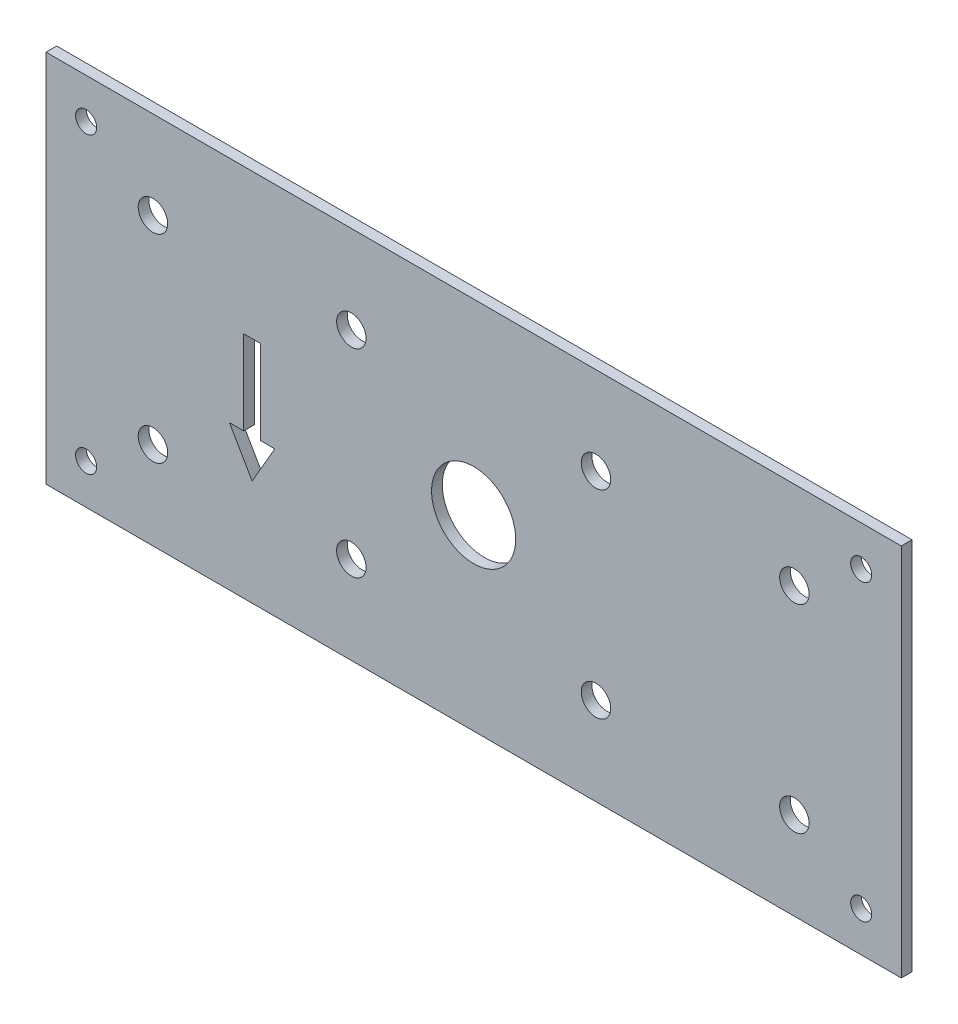
SolidWorks part; units mm, degrees
ref_plane "Front Plane" through (0, 0, 0) normal (0, 0, 1) x (1, 0, 0)
ref_plane "Top Plane" through (0, 0, 0) normal (0, 1, 0) x (1, 0, 0)
ref_plane "Right Plane" through (0, 0, 0) normal (1, 0, 0) x (0, 0, -1)
sketch "Sketch2" plane through (0, 0, 0) normal (0, 0, 1) x (1, 0, 0)
  line L0 (-29.06, 23.57) -> (-76.2, 23.57) construction
  line L1 (-101.6, -44.45) -> (101.6, -44.45)
  line L2 (-101.6, -44.45) -> (-101.6, 44.45)
  line L3 (-101.6, 44.45) -> (101.6, 44.45)
  line L4 (101.6, -44.45) -> (101.6, 44.45)
  line L5 (-101.6, -44.45) -> (101.6, 44.45) construction
  line L6 (-101.6, 44.45) -> (101.6, -44.45) construction
  line L7 (-76.2, 23.57) -> (-76.2, -23.57) construction
  line L8 (-76.2, -23.57) -> (-29.06, -23.57) construction
  line L9 (-29.06, -23.57) -> (-29.06, 23.57) construction
  line L10 (-76.2, 0) -> (-101.6, 0) construction
  line L12 (29.06, -23.57) -> (76.2, -23.57) construction
  line L13 (76.2, -23.57) -> (76.2, 23.57) construction
  line L14 (76.2, 23.57) -> (29.06, 23.57) construction
  line L15 (29.06, 23.57) -> (29.06, -23.57) construction
  line L17 (76.2, 0) -> (101.6, 0) construction
  circle A11 centre (-76.2, 23.57) radius 3.5
  circle A12 centre (-29.06, 23.57) radius 3.5
  circle A13 centre (-29.06, -23.57) radius 3.5
  circle A14 centre (-76.2, -23.57) radius 3.5
  circle A15 centre (29.06, -23.57) radius 3.5
  circle A16 centre (76.2, -23.57) radius 3.5
  circle A17 centre (76.2, 23.57) radius 3.5
  circle A18 centre (29.06, 23.57) radius 3.5
  circle A19 centre (0, 0) radius 10
  point P0 (0, 0)
  point P17 (101.6, 0)
  point P23 (-101.6, 0)
  dimension "D3" = 7
  dimension "D6" = 20
  dimension "D1" = 47.14
  dimension "D2" = 88.9
  dimension "D4" = 203.2
  dimension "D5" = 25.4
extrude "Boss-Extrude1" add sketch "Sketch2" along normal mid plane 2.54
sketch "Sketch3" plane through (0, 0, 1.27) normal (0, 0, 1) x (1, 0, 0)
  line L0 (-101.6, 34.925) -> (-92.075, 34.925) construction
  line L1 (-101.6, 44.45) -> (-101.6, -44.45) construction
  line L2 (-92.075, 34.925) -> (-92.075, 44.45) construction
  line L3 (101.6, 44.45) -> (-101.6, 44.45) construction
  line L4 (92.075, 44.45) -> (92.075, 34.925) construction
  line L5 (92.075, 34.925) -> (101.6, 34.925) construction
  line L6 (101.6, -44.45) -> (101.6, 44.45) construction
  line L7 (92.075, -44.45) -> (92.075, -34.925) construction
  line L8 (-101.6, -44.45) -> (101.6, -44.45) construction
  line L9 (92.075, -34.925) -> (101.6, -34.925) construction
  line L10 (-92.075, -44.45) -> (-92.075, -34.925) construction
  line L11 (-92.075, -34.925) -> (-101.6, -34.925) construction
  circle A0 centre (-92.075, 34.925) radius 2.5
  circle A1 centre (-92.075, -34.925) radius 2.5
  circle A2 centre (92.075, -34.925) radius 2.5
  circle A3 centre (92.075, 34.925) radius 2.5
  dimension "D2" = 5
  dimension "D1" = 9.525
extrude "Cut-Extrude1" cut sketch "Sketch3" against normal through all
sketch "Sketch4" plane through (0, 0, 1.27) normal (0, 0, 1) x (1, 0, 0)
  line L0 (-76.2, 23.57) -> (-29.06, -23.57) construction
  line L1 (-54.63, -10) -> (-58.0088, -10)
  line L2 (-54.63, -10) -> (-50.63, -10)
  line L3 (-54.63, -10) -> (-54.63, 10)
  line L4 (-54.63, 10) -> (-50.63, 10)
  line L5 (-50.63, -10) -> (-50.63, 10)
  line L6 (-54.63, -10) -> (-50.63, 10) construction
  line L7 (-54.63, 10) -> (-50.63, -10) construction
  line L8 (-58.0088, -10) -> (-52.63, -19.3163)
  line L9 (-52.63, -19.3163) -> (-47.2512, -10)
  line L10 (-50.63, -10) -> (-47.2512, -10)
  point P2 (0, 0)
  point P3 (-52.63, 0)
  point P4 (-52.63, -20.2489)
  point P14 (-50.63, 9.2211)
  point P15 (0, 0)
  point P16 (-52.63, -19.3163)
  dimension "D1" = 4
  dimension "D2" = 20
  dimension "D3" = 60
extrude "Cut-Extrude2" cut sketch "Sketch4" against normal through all both and the other way through all contours L10 L2 L1 L8 L9 | L2 L5 L4 L3 region at (-52.63, -13.1054, 1.27) region at (-52.63, 0, 1.27)
